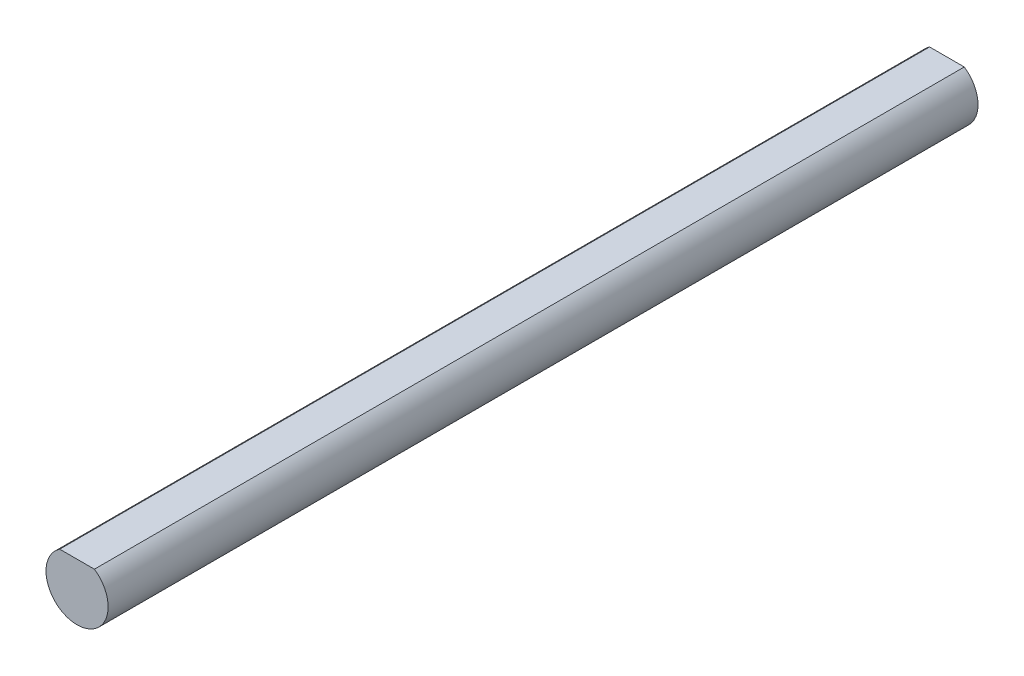
SolidWorks part; units mm, degrees
note: The reader was unsure of these and kept them because the rebuilt part matched: shared geometry of "Sketch1<6>".
other "Defeature"
material "Stainless Steel (ferritic)"
ref_plane "Front Plane" through (0, 0, 0) normal (0, 0, 1) x (1, 0, 0)
ref_plane "Top Plane" through (0, 0, 0) normal (0, 1, 0) x (1, 0, 0)
ref_plane "Right Plane" through (0, 0, 0) normal (1, 0, 0) x (0, 0, -1)
sketch "Sketch1" plane through (0, 0, 0) normal (0, 0, 1) x (1, 0, 0)
  line L0 (-1.3115, 1.95) -> (1.3115, 1.95)
  line L1 (-1.3115, -2.35) -> (1.3115, -2.35) construction
  arc A0 (-1.3115, 1.95) -> (1.3115, 1.95) centre (0, 0) ccw
  point P1 (0, -2.35)
  dimension "D1" = 4.3
  dimension "D2" = 2.35
extrude "Boss-Extrude1" add sketch "Sketch1" along normal mid plane 100
extrude "Cut-Extrude3" cut sketch "Sketch1<6>" against normal blind 34.214 from surface at 50 starting at face at (0, -0.2, 50)
sketch "Sketch1<6>" plane through (0, 0, 0) normal (0, 0, 1) x (1, 0, 0) same geometry as "Sketch1"
